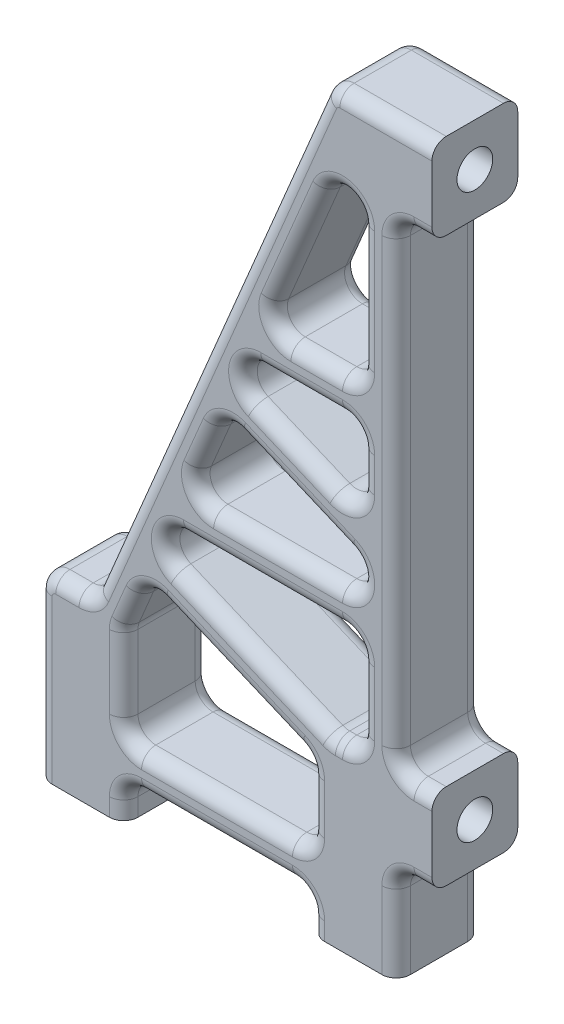
SolidWorks part; units mm, degrees
ref_plane "Спереди" through (0, 0, 0) normal (0, 0, 1) x (1, 0, 0)
ref_plane "Сверху" through (0, 0, 0) normal (0, 1, 0) x (1, 0, 0)
ref_plane "Справа" through (0, 0, 0) normal (1, 0, 0) x (0, 0, -1)
sketch "Эскиз1" plane through (0, 0, 0) normal (0, 0, 1) x (1, 0, 0)
  line L0 (-18.4277, 49) -> (76.1089, 49) construction
  line L1 (-18.4277, 9.63) -> (76.1089, 9.63) construction
  line L2 (-18.4277, 3.28) -> (76.1089, 3.28) construction
  line L3 (3, 87.6877) -> (3, -19.2431) construction
  line L4 (22.05, 87.6877) -> (22.05, -19.2431) construction
  line L5 (27.55, 46) -> (27.55, 52)
  line L6 (19.05, 0) -> (25.05, 0)
  line L7 (0, 0) -> (6, 0)
  line L8 (25.05, 0) -> (25.05, 5.38)
  line L9 (27.55, 6.63) -> (27.55, 12.63)
  line L10 (25.05, 44.75) -> (25.05, 13.88)
  line L11 (7.25, 2.5) -> (17.8, 2.5)
  line L12 (0, 0) -> (0, 11.38)
  line L13 (4.0295, 13.3949) -> (19.9616, 51.2351)
  line L14 (21.1137, 52) -> (27.55, 52)
  line L15 (19.05, 6.25) -> (19.05, 11.38)
  line L16 (17.8, 5) -> (7.25, 5)
  line L17 (6, 6.25) -> (6, 11.38)
  line L18 (6.0979, 11.8651) -> (20.1479, 45.2351)
  line L19 (20.3, 12.63) -> (21.3, 12.63)
  line L20 (22.55, 13.88) -> (22.55, 44.75)
  line L21 (28.4544, 46) -> (19.3381, 46) construction
  line L22 (27.55, 46) -> (26.3, 46)
  line L23 (27.55, 12.63) -> (26.3, 12.63)
  line L24 (27.55, 6.63) -> (26.3, 6.63)
  line L25 (19.05, 0) -> (19.05, 1.25)
  line L26 (6, 0) -> (6, 1.25)
  line L27 (1.25, 12.63) -> (2.8775, 12.63)
  arc A0 (26.3, 46) -> (25.05, 44.75) centre (26.3, 44.75) ccw
  arc A1 (25.05, 13.88) -> (26.3, 12.63) centre (26.3, 13.88) ccw
  arc A2 (25.05, 5.38) -> (26.3, 6.63) centre (26.3, 5.38) cw
  arc A3 (6, 1.25) -> (7.25, 2.5) centre (7.25, 1.25) cw
  arc A4 (17.8, 2.5) -> (19.05, 1.25) centre (17.8, 1.25) cw
  arc A5 (1.25, 12.63) -> (0, 11.38) centre (1.25, 11.38) ccw
  arc A6 (19.9616, 51.2351) -> (21.1137, 52) centre (21.1137, 50.75) cw
  arc A7 (19.05, 6.25) -> (17.8, 5) centre (17.8, 6.25) cw
  arc A8 (7.25, 5) -> (6, 6.25) centre (7.25, 6.25) cw
  arc A9 (20.1479, 45.2351) -> (22.55, 44.75) centre (21.3, 44.75) cw
  arc A10 (6, 11.38) -> (6.0979, 11.8651) centre (7.25, 11.38) cw
  arc A11 (19.05, 11.38) -> (20.3, 12.63) centre (20.3, 11.38) cw
  arc A12 (21.3, 12.63) -> (22.55, 13.88) centre (21.3, 13.88) ccw
  arc A13 (2.8775, 12.63) -> (4.0295, 13.3949) centre (2.8775, 13.88) ccw
  point P13 (27.55, 49)
  point P16 (22.05, 0)
  point P19 (3, 0)
  point P31 (27.55, 9.63)
  dimension "D6" = 1.25
  dimension "D7" = 1.25
  dimension "D9" = 2.5
  dimension "D1" = 39.37
  dimension "D2" = 6.35
  dimension "D3" = 19.05
  dimension "D4" = 49
  dimension "D5" = 6
  dimension "D8" = 2.5
  dimension "D10" = 2.5
  dimension "D11" = 2.5
  dimension "D12" = 2.5
extrude "Бобышка-Вытянуть1" add sketch "Эскиз1" along normal blind 6
sketch "Эскиз2" plane through (0, 0, 0) normal (0, 0, 1) x (1, 0, 0)
  line L0 (7.5779, 15.3802) -> (19.05, 10.55)
  line L2 (20.5524, 12.63) -> (9.7001, 17.1992)
  line L5 (20.7851, 12.5321) -> (19.8149, 10.2279) construction
  line L6 (20.3, 12.63) -> (20.5524, 12.63)
  line L7 (10.1852, 19.6013) -> (22.55, 19.6013)
  line L8 (7.5779, 15.3802) -> (10.4078, 22.1013)
  line L9 (10.4078, 22.1013) -> (21.3, 22.1013)
  line L10 (12.98, 28.2106) -> (21.7851, 24.5033)
  line L11 (15.1022, 30.0296) -> (22.55, 26.8938)
  line L12 (22.55, 32.4317) -> (15.5872, 32.4317)
  line L13 (15.8098, 34.9317) -> (22.55, 34.9317)
  line L14 (22.55, 13.88) -> (22.55, 44.75) construction
  line L17 (22.55, 34.9317) -> (22.55, 32.4317)
  line L18 (15.8098, 34.9317) -> (12.98, 28.2106)
  line L19 (22.55, 26.8938) -> (22.55, 19.6013)
  line L21 (20.1479, 45.2351) -> (6.0979, 11.8651) construction
  line L22 (20.3, 12.63) -> (21.3, 12.63) construction
  line L23 (19.05, 11.38) -> (19.05, 10.55)
  line L24 (19.05, 6.25) -> (19.05, 11.38) construction
  arc A1 (19.05, 11.38) -> (20.3, 12.63) centre (20.3, 11.38) cw
  arc A2 (9.7001, 17.1992) -> (10.1852, 19.6013) centre (10.1852, 18.3513) cw
  arc A3 (21.3, 22.1013) -> (21.7851, 24.5033) centre (21.3, 23.3513) ccw
  arc A4 (15.5872, 32.4317) -> (15.1022, 30.0296) centre (15.5872, 31.1817) ccw
  arc A6 (20.3, 12.63) -> (19.05, 11.38) centre (20.3, 11.38) ccw construction
  point P6 (20.3, 11.38)
  point P9 (20.3, 11.38)
  dimension "D2" = 1.25
  dimension "D1" = 2.5
  dimension "D3" = 2.5
  dimension "D4" = 2.5
  dimension "D5" = 2.5
extrude "Бобышка-Вытянуть2" add sketch "Эскиз2" along normal blind 6 contours L2 A2 L8 L0 | A3 L9 L8 A2 L7 L19 | A4 L18 L10 A3 L19 L11 | L13 L18 A4 L12 L17 | L17 | L2 L0 region at (13.6573, 14.1992, 0) region at (18.8835, 33.6423, 0) region at (17.9752, 27.4547, 0) region at (16.2498, 20.8448, 0)
fillet "Скругление1" radius 1.25 10 edges at (19.05, 10.55, 3) (20.5524, 12.63, 3) (7.5779, 15.3802, 3) (22.55, 19.6013, 3) (10.4078, 22.1013, 3) (12.98, 28.2106, 3) (22.55, 26.8938, 3) (22.55, 32.4317, 3) (15.8098, 34.9317, 3) (22.55, 34.9317, 3)
sketch "Эскиз3" plane through (27.55, 0, 0) normal (1, 0, 0) x (0, 0, -1)
  line L0 (-6, 6.63) -> (0, 12.63) construction
  line L1 (0, 6.63) -> (-6, 12.63) construction
  line L2 (-6, 46) -> (0, 52) construction
  line L3 (0, 46) -> (-6, 52) construction
  circle A0 centre (-3, 49) radius 1.25
  circle A1 centre (-3, 9.63) radius 1.25
  point P12 (-3, 9.63)
  point P21 (-3, 49)
  dimension "D1" = 2.5
extrude "Вырез-Вытянуть1" cut sketch "Эскиз3" against normal blind 7 contours A1 | A0
sketch "Эскиз4" plane through (0, 0, 0) normal (0, -1, 0) x (1, 0, 0)
  line L0 (25.05, 6) -> (19.05, 0) construction
  line L1 (19.05, 6) -> (25.05, 0) construction
  line L2 (0, 6) -> (6, 0) construction
  line L3 (6, 6) -> (0, 0) construction
  circle A0 centre (3, 3) radius 1.25
  circle A1 centre (22.05, 3) radius 1.25
  point P16 (3, 3)
  point P17 (22.05, 3)
  dimension "D1" = 2.5
extrude "Вырез-Вытянуть2" cut sketch "Эскиз4" against normal blind 7
fillet "Скругление7" radius 1 112 edges at (21.5474, 45.9753, 6) (14.362, 31.4291, 6) (18.4436, 32.4317, 6) (17.9586, 26.1144, 6) (22.5253, 23.1039, 6) (15.0099, 14.9636, 6) (8.9599, 18.5987, 6) (15.7426, 19.6013, 6) (6, 0.625, 6) (24.3318, 52, 6) (20.4222, 51.7914, 6) (0, 5.69, 6) (19.4962, 34.9317, 6) (17.9586, 28.827, 6) (16.7952, 22.1013, 6) (25.05, 29.315, 6) (25.05, 2.69, 6) (12.525, 2.5, 6) (11.9956, 32.315, 6) (16.6511, 35.4902, 6) (18.3442, 40.9509, 6) (22.55, 40.4658, 6) (22.1839, 35.2978, 6) (22.1839, 32.0656, 6) (22.55, 29.979, 6) (21.9914, 27.735, 6) (11.249, 22.6598, 6) (11.8166, 25.4474, 6) (13.1754, 27.7311, 6) (16.6511, 35.4902, 0) (18.3442, 40.9509, 0) (21.5474, 45.9753, 0) (22.55, 40.4658, 0) (22.1839, 35.2978, 0) (14.362, 31.4291, 0) (18.4436, 32.4317, 0) (22.1839, 32.0656, 0) (22.55, 29.979, 0) (21.9914, 27.735, 0) (11.249, 22.6598, 0) (11.8166, 25.4474, 0) (13.1754, 27.7311, 0) (17.9586, 26.1144, 0) (22.5253, 23.1039, 0) (20.5574, 12.6547, 0) (21.0524, 12.63, 0) (22.1839, 12.9961, 0) (22.55, 16.1156, 0) (22.1839, 19.2352, 0) (15.7426, 19.6013, 0) (8.9599, 18.5987, 0) (6.3661, 5.3661, 0) (6, 8.815, 0) (6.0247, 11.6274, 0) (6.5954, 13.0466, 0) (7.7733, 14.9007, 0) (13.5075, 12.8836, 0) (18.8414, 10.4115, 0) (19.05, 7.985, 0) (18.6839, 5.3661, 0) (24.3318, 52, 0) (20.4222, 51.7914, 0) (0, 5.69, 0) (6, 0.625, 0) (20.5574, 12.6547, 6) (21.0524, 12.63, 6) (22.1839, 12.9961, 6) (22.55, 16.1156, 6) (22.1839, 19.2352, 6) (18.6839, 5.3661, 6) (12.525, 5, 6) (6.3661, 5.3661, 6) (6, 8.815, 6) (6.0247, 11.6274, 6) (6.5954, 13.0466, 6) (7.7733, 14.9007, 6) (13.5075, 12.8836, 6) (18.8414, 10.4115, 6) (19.4962, 34.9317, 0) (17.9586, 28.827, 0) (16.7952, 22.1013, 0) (15.0099, 14.9636, 0) (12.525, 5, 0) (11.9956, 32.315, 0) (12.525, 2.5, 0) (25.05, 2.69, 0) (25.05, 29.315, 0) (19.05, 7.985, 6) (0.3661, 12.2639, 0) (2.0637, 12.63, 0) (3.5689, 12.8386, 0) (6.3661, 2.1339, 0) (19.05, 0.625, 0) (18.6839, 2.1339, 0) (26.925, 6.63, 0) (25.4161, 6.2639, 0) (26.925, 12.63, 0) (25.4161, 12.9961, 0) (26.925, 46, 0) (25.4161, 45.6339, 0) (26.925, 12.63, 6) (25.4161, 12.9961, 6) (26.925, 46, 6) (25.4161, 45.6339, 6) (26.925, 6.63, 6) (25.4161, 6.2639, 6) (0.3661, 12.2639, 6) (2.0637, 12.63, 6) (3.5689, 12.8386, 6) (6.3661, 2.1339, 6) (19.05, 0.625, 6) (18.6839, 2.1339, 6)
